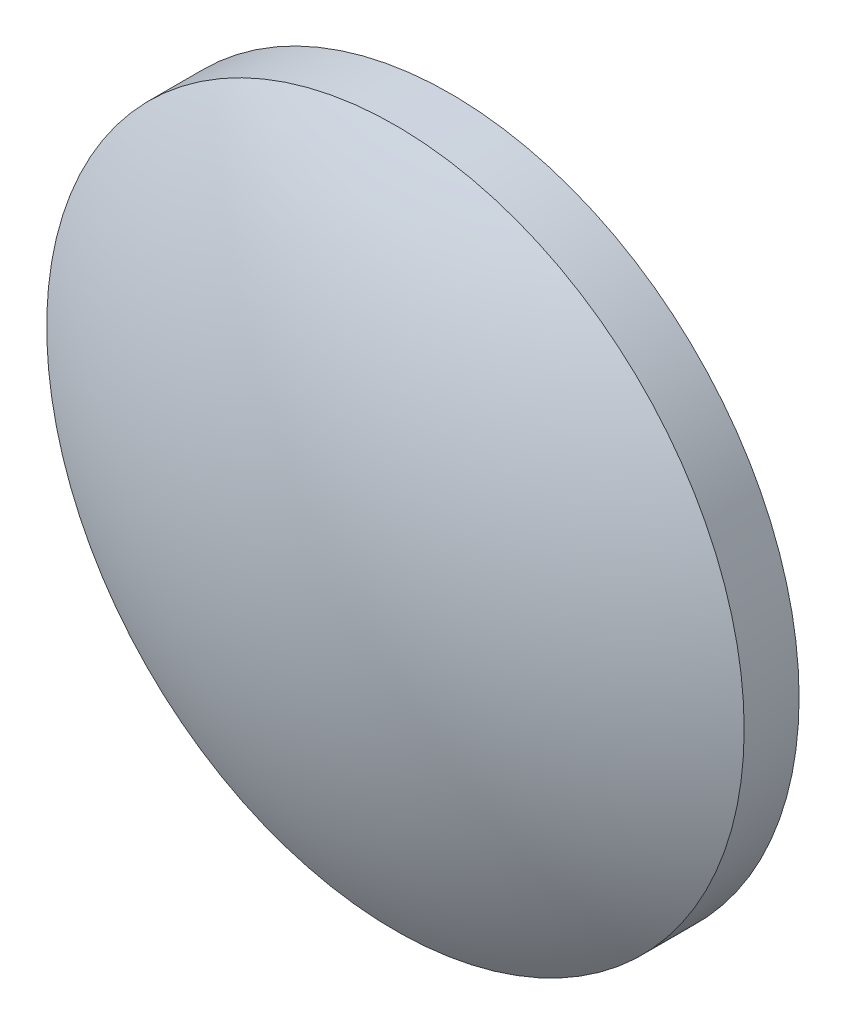
SolidWorks part; units mm, degrees
ref_plane "前视基准面" through (0, 0, 0) normal (0, 0, 1) x (1, 0, 0)
ref_plane "上视基准面" through (0, 0, 0) normal (0, 1, 0) x (1, 0, 0)
ref_plane "右视基准面" through (0, 0, 0) normal (1, 0, 0) x (0, 0, -1)
sketch "草图1" plane through (0, 0, 0) normal (0, 0, 1) x (1, 0, 0)
  circle A0 centre (0, 0) radius 12.7
extrude "凸台-拉伸1" add sketch "草图1" along normal blind 2
dome "圆顶1" faces to dome 1 distance 3.5 reverse direction no elliptical dome no face at (12.7, 0, 2) parameters "D1"=3.5
